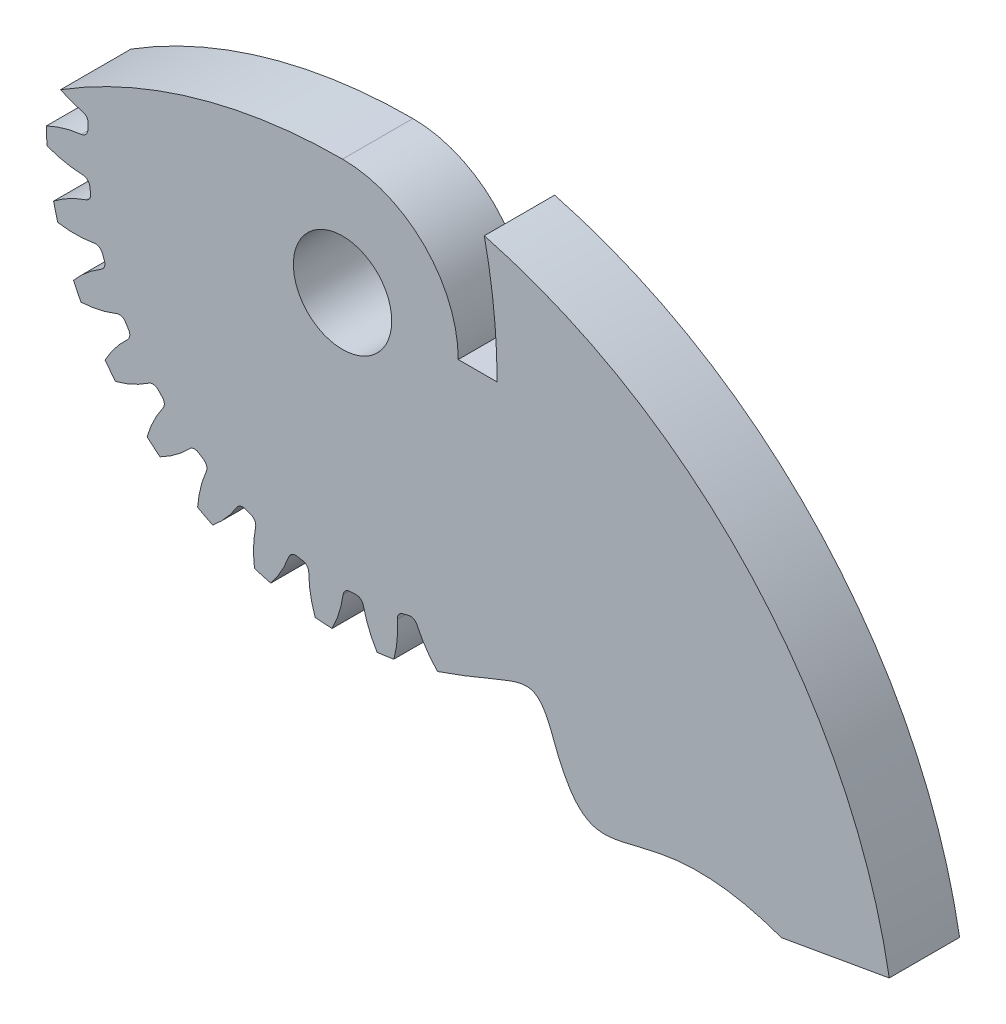
SolidWorks part; units mm, degrees
material "ABS"
ref_plane "Front" through (0, 0, 0) normal (0, 0, 1) x (1, 0, 0)
ref_plane "Top" through (0, 0, 0) normal (0, 1, 0) x (1, 0, 0)
ref_plane "Right" through (0, 0, 0) normal (1, 0, 0) x (0, 0, -1)
sketch "Sketch3" plane through (0, 0, 0) normal (0, 0, 1) x (1, 0, 0)
  circle A0 centre (0, 0) radius 40.64
  dimension "od" = 81.28
extrude "gearBody" add sketch "Sketch3" along normal blind 9.652
sketch "Sketch2" plane through (0, 0, 0) normal (0, 0, 1) x (1, 0, 0)
  line L0 (0, 0) -> (34.0786, 14.1158) construction
  line L1 (45.4751, -11.4855) -> (0, 0) construction
  line L2 (0, 0) -> (36.3143, 0) construction
  line L3 (38.0972, -0.458) -> (37.8451, -4.4001) construction
  line L5 (37.9712, -2.4291) -> (0, 0) construction
  line L7 (0, 0) -> (36.8864, 0) construction
  arc A0 (36.879, -0.7403) -> (36.6727, -3.9649) centre (0, 0) ccw construction
  arc A1 (40.637, 0.4947) -> (40.2427, -5.6687) centre (0, 0) ccw construction
  arc A2 (38.0972, -0.458) -> (37.8451, -4.4001) centre (0, 0) ccw construction
  arc A3 (34.9015, -2.6404) -> (34.9534, -1.8283) centre (0, 0) ccw
  arc A4 (45.4751, -11.4855) -> (35.6466, -3.6712) centre (32.0022, -18.3431) ccw
  arc A5 (45.4751, -11.4855) -> (46.5679, 5.5974) centre (0, 0) ccw
  arc A6 (46.5679, 5.5974) -> (35.8238, -0.9008) centre (34.0786, 14.1158) cw
  arc A7 (34.9534, -1.8283) -> (35.8238, -0.9008) centre (35.9376, -1.8798) cw
  arc A8 (35.6466, -3.6712) -> (34.9015, -2.6404) centre (35.8842, -2.7147) cw
  point P6 (46.5679, 5.5974)
  point P22 (45.4751, -11.4855)
  dimension "baseDia" = 73.7729
  dimension "od" = 81.28
  dimension "pd" = 76.2
  dimension "rd" = 70.0024
  dimension "rFillet" = 0.9855
  dimension "pointX" = 46.5679
  dimension "pointY" = 5.5974
  dimension "CTT" = 3.9421
  dimension "flankCenterAngle" = 22.5
extrude "toothCut" cut sketch "Sketch2" along normal through all
pattern_circular "CirPattern1" count 30 over 360 about axis through (0, 0, 9.652) along (0, 0, -1) of "toothCut"
sketch "hub1Dia" plane through (0, 0, 0) normal (0, 0, -1) x (-1, 0, 0)
  circle A0 centre (0, 0) radius 12.7
  dimension "hub1Dia" = 25.4
sketch "hub2Dia" plane through (0, 0, 9.652) normal (0, 0, 1) x (1, 0, 0)
  circle A0 centre (0, 0) radius 12.7
  dimension "hub2dia" = 25.4
sketch "boreDia" plane through (0, 0, 0) normal (0, 0, 1) x (1, 0, 0)
  circle A0 centre (0, 0) radius 6.7469
  dimension "boreDia" = 13.4937
extrude "bore" cut sketch "boreDia" against normal mid plane 25400
sketch "Sketch4" plane through (0, 0, 9.652) normal (0, 0, 1) x (1, 0, 0)
  circle A0 centre (0, -57.15) radius 76.1746
  arc A2 (-41.7195, 6.5842) -> (41.7195, 6.5842) centre (0, 0) cw
  dimension "D1" = 152.3492
  dimension "D2" = 57.15
extrude "Cut-Extrude1" cut sketch "Sketch4" against normal through all contours A0 region at (0, 26.0638, 9.652)
sketch "Sketch5" plane through (0, 0, 9.652) normal (0, 0, 1) x (1, 0, 0)
  line L0 (0, 19.0246) -> (21.5163, 3.7176)
  line L1 (21.5163, 3.7176) -> (8.9608, -26.928)
  line L2 (8.9608, -26.928) -> (13.028, -38.4952)
  line L3 (0, 0) -> (0, -57.15) construction
  line L4 (0, -57.15) -> (-54.1615, -3.586) construction
  line L5 (0, -57.15) -> (65.9691, -95.2373) construction
  line L9 (0, -57.15) -> (75.0173, -43.9224) construction
  line L12 (60.232, -46.5295) -> (75.0173, -43.9224)
  line L13 (0, -57.15) -> (29.696, -40.005) construction
  line L14 (29.696, -40.005) -> (26.521, -34.5057) construction
  circle A1 centre (0, -57.15) radius 76.1746 construction
  arc A5 (0, 19.0246) -> (75.0173, -43.9224) centre (0, -57.15) cw
  circle A6 centre (0, -57.15) radius 21.59 construction
  circle A12 centre (49.4934, -85.725) radius 40.64 construction
  spline S0 degree 3 poles (13.028, -38.4952) (20.557, -35.948) (26.6517, -31.726) (34.6651, -56.7545) (39.5345, -39.0169) (60.232, -46.5295) knots 0 0 0 0 0.118515 0.218515 1 1 1 1
  point P28 (21.569, -56.1981)
  dimension "D1" = 43.18
  dimension "D3" = 81.28
  dimension "D6" = 152.3492
  dimension "D2" = 120
  dimension "D4" = 57.15
  dimension "D8" = 57.15
  dimension "D7" = 60
  dimension "D9" = 34.29
  dimension "D10" = 6.35
  dimension "D5" = 80
extrude "Boss-Extrude1" add sketch "Sketch5" against normal up to surface (9.652 mm away) up to face at (6.7469, 0, 0)
sketch "Sketch6" plane through (0, 0, 9.652) normal (0, 0, 1) x (1, 0, 0)
  line L1 (-41.2993, 3.0747) -> (-42.3397, 6.1739)
  line L2 (15.875, 0) -> (21.209, 0)
  circle A0 centre (0, -57.15) radius 76.1746 construction
  arc A1 (75.0173, -43.9224) -> (-34.0662, 10.9827) centre (0, -57.15) ccw construction
  circle A2 centre (0, 0) radius 15.875 construction
  arc A3 (0, 15.875) -> (15.875, 0) centre (0, 0) cw
  arc A4 (19.4523, 16.499) -> (-42.3397, 6.1739) centre (0, -57.15) ccw
  arc A5 (0, 15.875) -> (-41.2993, 3.0747) centre (0, -57.15) ccw
  circle A6 centre (0, 0) radius 21.209 construction
  circle A8 centre (-57.15, 0) radius 78.359 construction
  arc A9 (21.209, 0) -> (19.4523, 16.499) centre (-57.15, 0) ccw
  dimension "D4" = 57.15
  dimension "D1" = 31.75
  dimension "D2" = 42.418
  dimension "D3" = 156.718
extrude "Cut-Extrude2" cut sketch "Sketch6" against normal through all
equation "\"Bodytube_OD\"= 6.17in"
equation "\"Bodytube_ID\"= 5.998in"
equation "\"Fwd_Tube_Length\"= 40in"
equation "\"Mid_Tube_Length\"= 1in"
equation "\"Aft_Section_Length\"= 39in"
equation "\"Mid_Coupler_Length\"= 13in"
equation "\"Aft_Lower_Length\"= 22in"
equation "\"AB_Coupler_OD_Length\"= 1in"
equation "\"AB_Coupling_Section_Length\"= 0.375in"
equation "\"AB_Coupler_Length\"= \"AB_Coupler_OD_Length\" + \"AB_Coupling_Section_Length\" * 2"
equation "\"Cutout_Angle\"= 80"
equation "\"AB_Paddle_Height\"= 0.375in"
equation "\"AB_Coupler_Num_Screws\"= 6"
equation "\"Num_Cutouts\"= 3"
equation "\"AB_Coupler_OD\"= 6.17in"
equation "\"AB_Coupler_ID\"= 5.75in"
equation "\"AB_Coupler_Surface_Diameter\"= 5.998in"
equation "\"AB_Coupling_Screw_Diameter\"= 0.1065in"
equation "\"AB_Central_Bushing_Length\"= .75in"
equation "\"Lead_Screw_Dist\"= 3.4in"
equation "\"Lead_Screw_Diam\"= 0.386in"
equation "\"Lead_Screw_Length\"= (\"Mid_Coupler_Length\" + 2*0.375in + 2*0.5in)"
equation "\"Paddle_Pin_Offset\"= .25in"
equation "\"Paddle_Pin_Radius\"= 2.25in"
equation "\"Fwd_BKHD_From_Top\"= 18in"
equation "\"D1@Sketch4\"=\"Bodytube_ID\""
equation "\"D2@Sketch4\"=\"Paddle_Pin_Radius\""
equation "\"D3@Sketch5\"=\"Paddle_Gear_OD\""
equation "\"D4@Sketch5\"=\"Paddle_Pin_Radius\""
equation "\"Motor_OD\"= 4in"
equation "\"Aft_Upper_Length\"= \"Aft_Section_Length\" - \"Aft_Lower_Length\" - \"AB_Coupler_OD_Length\""
equation "\"Paddle_Gear_OD\"= 3.2in"
equation "\"D5@Sketch5\"=\"Cutout_Angle\""
equation "\"D6@Sketch5\"=\"Bodytube_ID\""
equation "\"D1@Sketch6\"=\"AB_Coupler_ID\"-2*\"Paddle_Pin_Radius\""
equation "\"D2@Sketch6\"=\"Bodytube_OD\"-2*\"Paddle_Pin_Radius\""
equation "\"D3@Sketch6\"=\"Bodytube_OD\""
equation "\"D4@Sketch6\"=\"Paddle_Pin_Radius\""
equation "\"D8@Sketch5\"=\"Paddle_Pin_Radius\""
equation "\"Drive_Gear_OD\"= 1.7in"
equation "\"Fin_Thickness\"= .118in"
equation "\"Guiderail_Cutout_Diameter\"= 1.5in"
equation "\"DB9_Hole_Dist\"= 25mm"
equation "\"D1@Sketch5\"=\"Drive_Gear_OD\""
